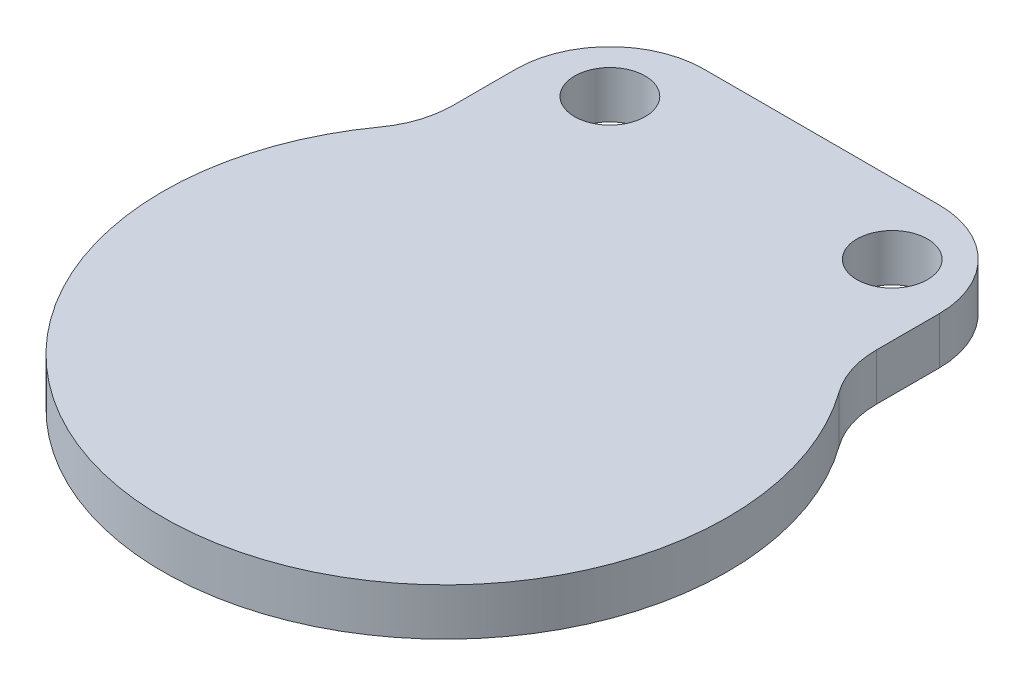
SolidWorks part; units mm, degrees
ref_plane "Спереди" through (0, 0, 0) normal (0, 0, 1) x (1, 0, 0)
ref_plane "Сверху" through (0, 0, 0) normal (0, 1, 0) x (1, 0, 0)
ref_plane "Справа" through (0, 0, 0) normal (1, 0, 0) x (0, 0, -1)
sketch "Sketch1" plane through (0, 0, 0) normal (0, 1, 0) x (1, 0, 0)
  line L0 (0, 0) -> (0, 13) construction
  line L1 (0, 13) -> (6, 13) construction
  line L2 (0, 13) -> (-6, 13) construction
  line L3 (-9, 10) -> (-9, 7.9373)
  line L4 (-9, 16) -> (9, 16)
  line L5 (-9, 16) -> (-9, 10)
  line L6 (-9, 10) -> (9, 10) construction
  line L7 (9, 16) -> (9, 10)
  line L8 (-9, 16) -> (9, 10) construction
  line L9 (-9, 10) -> (9, 16) construction
  line L10 (9, 10) -> (9, 7.9373)
  circle A0 centre (0, 0) radius 10 construction
  arc A1 (-9, 7.9373) -> (9, 7.9373) centre (0, 0) ccw
  circle A2 centre (-6, 13) radius 1.5
  circle A3 centre (6, 13) radius 1.5
  dimension "D1" = 20
  dimension "D2" = 2
  dimension "D3" = 3
  dimension "D5" = 3
  dimension "D6" = 12
  dimension "D7" = 3
extrude "Boss-Extrude1" add sketch "Sketch1" along normal blind 2
fillet "Fillet2" radius 4 4 edges at (-9, 1, -7.9373) (-9, 1, -16) (9, 1, -16) (9, 1, -7.9373)
